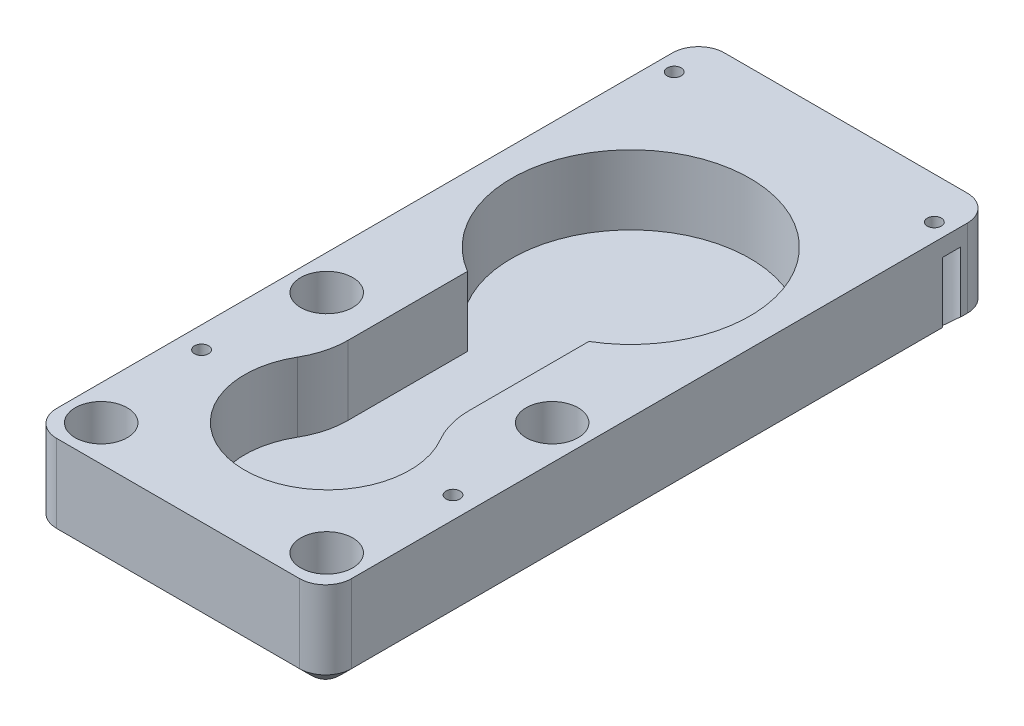
SolidWorks part; units mm, degrees
ref_plane "前视基准面" through (0, 0, 0) normal (0, 0, 1) x (1, 0, 0)
ref_plane "上视基准面" through (0, 0, 0) normal (0, 1, 0) x (1, 0, 0)
ref_plane "右视基准面" through (0, 0, 0) normal (1, 0, 0) x (0, 0, -1)
other "Configuration Table"
sketch "草图1" plane through (0, 0, 0) normal (0, 1, 0) x (1, 0, 0)
  line L0 (0, 0) -> (28, 0)
  line L1 (-3, 77) -> (-3, 3)
  line L2 (31, 77) -> (-3, 77)
  line L3 (31, 3) -> (31, 77)
  arc A0 (28, 0) -> (31, 3) centre (28, 3) ccw
  arc A1 (-3, 3) -> (0, 0) centre (0, 3) ccw
  point P6 (0, 0)
  point P7 (12.8308, 38.262)
  point P9 (0, 0)
  point P11 (0, 0)
  point P12 (0, 0)
  point P13 (0, 0)
  point P14 (-22.5489, 32.9875)
  point P15 (0, 0)
  point P16 (-22.5489, 38.262)
  dimension "D1" = 3
  dimension "D2" = 3
  dimension "D3" = 28
  dimension "D4" = 74
  dimension "D5" = 34
extrude "凸台-拉伸1" add sketch "草图1" along normal blind 12
extrude "切除-拉伸1" cut sketch "草图2" against normal blind 12
sketch "草图2" plane through (14, 12, -382.2) normal (0, 1, 0) x (1, 0, 0)
  circle A4 centre (13, -352.0691) radius 3
  circle A5 centre (-13, -352.0691) radius 3
  circle A6 centre (13, -378.0691) radius 3
  circle A7 centre (-13, -378.0691) radius 3
  circle A12 centre (-15, -310) radius 0.81
  circle A13 centre (15, -310) radius 0.81
  circle A14 centre (14.5, -365) radius 0.81
  circle A15 centre (-14.5, -365) radius 0.81
extrude "切除-拉伸2" cut sketch "草图3" against normal blind 8
sketch "草图3" plane through (14, 12, -382.2) normal (0, 1, 0) x (1, 0, 0)
  line L0 (-7, -341.8348) -> (-7, -355.6399)
  line L1 (7, -355.6399) -> (7, -341.8348)
  arc A10 (-8.2317, -360.1844) -> (-7, -355.6399) centre (-16, -355.6399) ccw
  arc A11 (7, -341.8348) -> (-7, -341.8348) centre (0, -330) ccw
  arc A12 (7, -355.6399) -> (8.2317, -360.1844) centre (16, -355.6399) ccw
  arc A13 (-8.2317, -360.1844) -> (8.2317, -360.1844) centre (0, -365) ccw
  point P15 (-9, -342.9252)
  point P17 (9, -342.9252)
  point P19 (-9.958, -359.5847)
fillet "圆角1" radius 3 2 edges at (-3, 6, -77) (31, 6, -77)
sketch "草图4" plane through (0, 0, 0) normal (0, -1, 0) x (1, 0, 0)
  circle A0 centre (-0.5, -17.2) radius 2.25
  circle A1 centre (28.5, -17.2) radius 2.25
  circle A2 centre (-1, -72.2) radius 2.25
  circle A3 centre (29, -72.2) radius 2.25
  dimension "D1" = 4.5
  dimension "D2" = 4.5
  dimension "D3" = 4.5
  dimension "D4" = 4.5
extrude "切除-拉伸3" cut sketch "草图4" against normal blind 10
chamfer "倒角3" distance 3 angle 45 6 edges at (14, 0, 0) (31, 0, -73.6154) (31, 0, -37.0846) (14, 0, -77) (-3, 0, -37.0846) (-3, 0, -73.6154)
